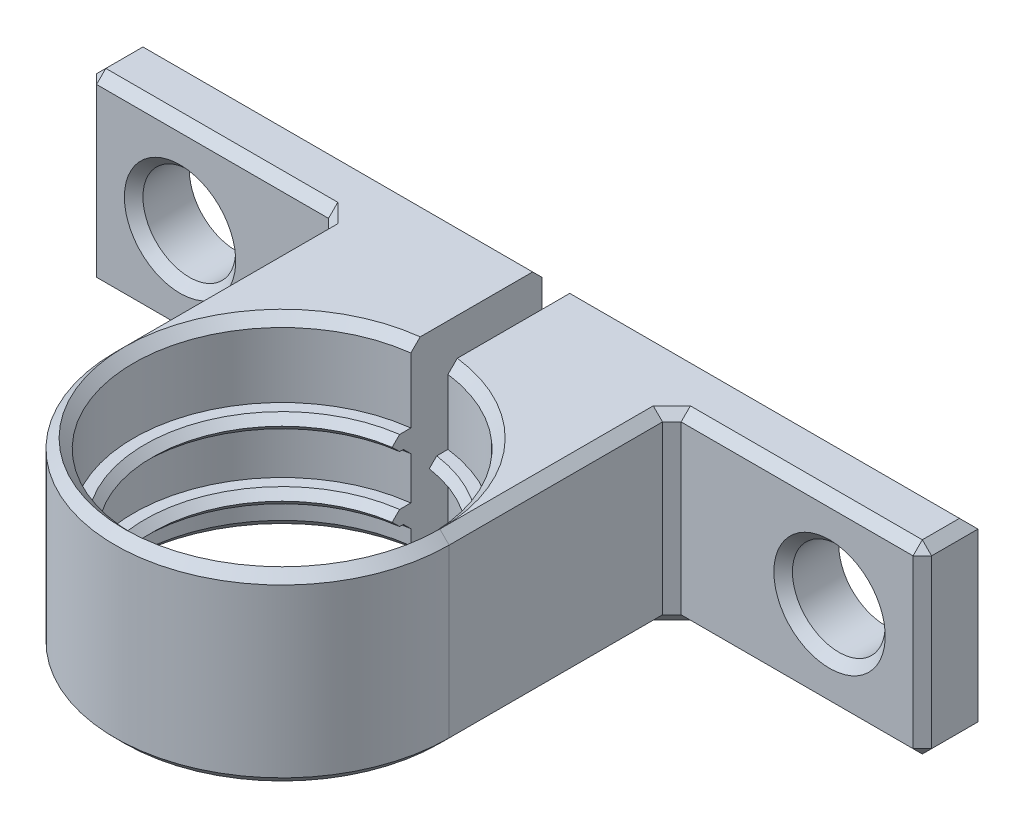
SolidWorks part; units mm, degrees
ref_plane "Alzado" through (0, 0, 0) normal (0, 0, 1) x (1, 0, 0)
ref_plane "Planta" through (0, 0, 0) normal (0, 1, 0) x (1, 0, 0)
ref_plane "Vista lateral" through (0, 0, 0) normal (1, 0, 0) x (0, 0, -1)
sketch "Croquis1" plane through (0, 0, 0) normal (0, 1, 0) x (1, 0, 0)
  line L0 (-9, 0) -> (-9, 12)
  line L1 (-9, 12) -> (-22.5, 12)
  line L2 (-22.5, 12) -> (-22.5, 15)
  line L3 (-22.5, 15) -> (22.5, 15)
  line L4 (22.5, 15) -> (22.5, 12)
  line L5 (22.5, 12) -> (9, 12)
  line L6 (9, 12) -> (9, 0)
  line L7 (0, 0) -> (0, 15696.111) construction
  line L8 (0, 0) -> (15696.111, 0) construction
  circle A0 centre (0, 0) radius 8
  arc A1 (-9, 0) -> (9, 0) centre (0, 0) ccw
  point P5 (0, 15)
  dimension "D1" = 16
  dimension "D2" = 9
  dimension "D3" = 45
  dimension "D4" = 3
  dimension "D5" = 15
extrude "Saliente-Extruir1" add sketch "Croquis1" along normal blind 10
sketch "Croquis2" plane through (0, 0, -15) normal (0, 0, -1) x (-1, 0, 0)
  line L0 (-20, 5) -> (49980, 5) construction
  line L1 (-22.5, 10) -> (-22.5, 0) construction
  line L2 (0, 0) -> (0, 50000) construction
  line L3 (-22.5, 0) -> (22.5, 0) construction
  circle A0 centre (-17.5, 5) radius 2.5
  circle A1 centre (17.5, 5) radius 2.5
  point P4 (-22.5, 5)
  point P9 (0, 0)
  dimension "D1" = 5
  dimension "D2" = 35
extrude "Cortar-Extruir2" cut sketch "Croquis2" against normal blind 10
sketch "Croquis3" plane through (0, 10, 0) normal (0, 1, 0) x (1, 0, 0)
  circle A0 centre (0, 0) radius 8
  circle A1 centre (0, 0) radius 7
  circle A2 centre (0, 0) radius 8 construction
  dimension "D1" = 1
extrude "Saliente-Extruir2" add sketch "Croquis3" against normal blind 0.8 from offset 4 offset against normal yes
pattern_linear "MatrizL1" count 2 spacing 3.5 along (0, -1, 0) of "Saliente-Extruir2"
chamfer "Chaflán1" distance 0.4 angle 45 4 edges at (0, 6, 7) (0, 5.2, 7) (0, 2.5, 7) (0, 1.7, 7)
chamfer "Chaflán2" distance 0.4 angle 45 2 edges at (0, 5.2, 8) (0, 1.7, 8)
chamfer "Chaflán3" distance 0.5 angle 45 24 edges at (0, 10, 8) (-9, 10, -6) (-15.75, 10, -12) (-22.5, 10, -13.5) (0, 10, -15) (22.5, 10, -13.5) (15.75, 10, -12) (9, 10, -6) (0, 10, 9) (15, 5, -12) (-20, 5, -12) (0, 0, 8) (9, 5, -12) (22.5, 5, -12) (-22.5, 5, -12) (9, 0, -6) (15.75, 0, -12) (22.5, 0, -13.5) (0, 0, -15) (-22.5, 0, -13.5) (-15.75, 0, -12) (0, 0, 9) (-9, 0, -6) (-9, 5, -12)
sketch "Croquis4" plane through (0, 10, 0) normal (0, 1, 0) x (1, 0, 0)
  line L0 (0, 0) -> (0, 50000) construction
  line L1 (-22.5, 15) -> (22.5, 15) construction
  line L2 (-1, 15) -> (1, 15)
  line L3 (-1, 15) -> (-1, 0)
  line L4 (-1, 0) -> (1, 0)
  line L5 (1, 15) -> (1, 0)
  line L6 (-1, 15) -> (1, 0) construction
  line L7 (-1, 0) -> (1, 15) construction
  point P3 (0, 7.5)
  point P8 (-2.3848, 15)
  dimension "D1" = 2
extrude "Cortar-Extruir3" cut sketch "Croquis4" against normal through all
